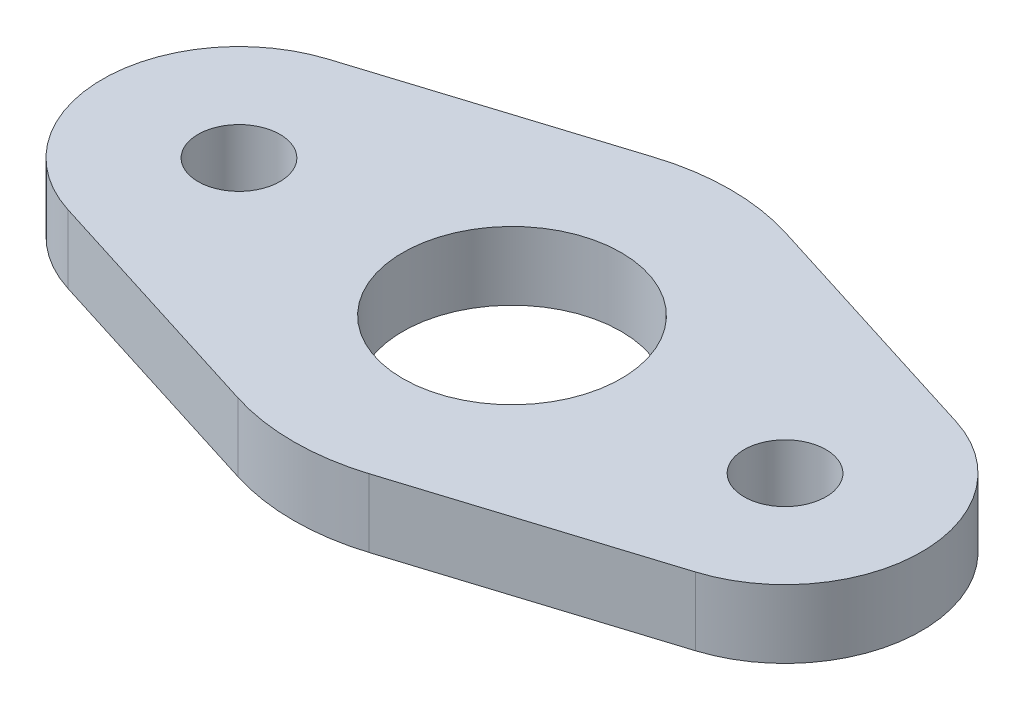
SolidWorks part; units mm, degrees
material "Maple"
ref_plane "Front Plane" through (0, 0, 0) normal (0, 0, 1) x (1, 0, 0)
ref_plane "Top Plane" through (0, 0, 0) normal (0, 1, 0) x (1, 0, 0)
ref_plane "Right Plane" through (0, 0, 0) normal (1, 0, 0) x (0, 0, -1)
sketch "Sketch1" plane through (0, 0, 0) normal (0, 1, 0) x (1, 0, 0)
  line L0 (0, 8) -> (0, -8) construction
  line L1 (-2.4, 7.6315) -> (-11.5, 4.7697)
  line L2 (-10.6506, 0) -> (10.6506, 0) construction
  line L3 (-2.4, -7.6315) -> (-11.5, -4.7697)
  line L4 (2.4, -7.6315) -> (11.5, -4.7697)
  line L5 (2.4, 7.6315) -> (11.5, 4.7697)
  arc A0 (-2.4, -7.6315) -> (2.4, -7.6315) centre (0, 0) ccw
  circle A1 centre (-10, 0) radius 1.5
  arc A2 (-11.5, 4.7697) -> (-11.5, -4.7697) centre (-10, 0) ccw
  circle A3 centre (10, 0) radius 1.5
  arc A4 (11.5, 4.7697) -> (11.5, -4.7697) centre (10, 0) cw
  arc A5 (2.4, 7.6315) -> (-2.4, 7.6315) centre (0, 0) ccw
  circle A6 centre (0, 0) radius 4
  dimension "D1" = 3
  dimension "D2" = 5
  dimension "D3" = 8
  dimension "D5" = 8
  dimension "D4" = 10
extrude "Boss-Extrude1" add sketch "Sketch1" along normal blind 2.5
